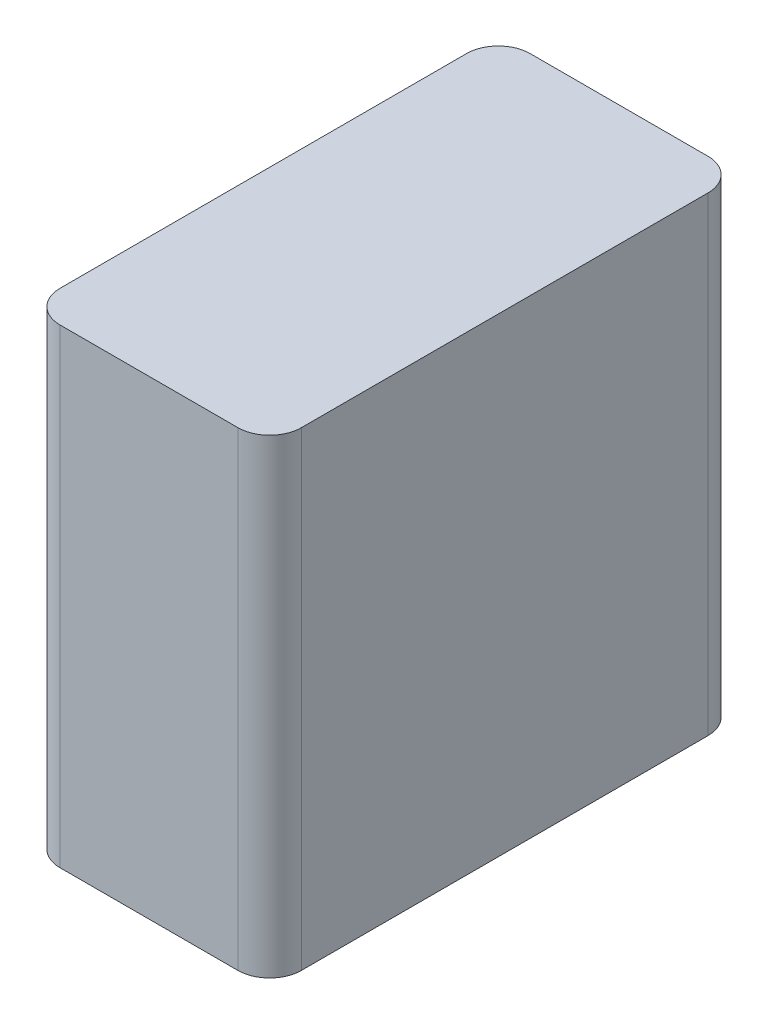
SolidWorks part; units mm, degrees
ref_plane "Front" through (0, 0, 0) normal (0, 0, 1) x (1, 0, 0)
ref_plane "Top" through (0, 0, 0) normal (0, 1, 0) x (1, 0, 0)
ref_plane "Right" through (0, 0, 0) normal (1, 0, 0) x (0, 0, -1)
sketch "Sketch1" plane through (0, 0, 0) normal (1, 0, 0) x (0, 0, -1)
  line L1 (0, 0) -> (74, 0)
  line L2 (0, 0) -> (0, 74)
  line L3 (0, 74) -> (74, 74)
  line L4 (74, 0) -> (74, 74)
  dimension "D1" = 74
  dimension "D2" = 74
extrude "Boss-Extrude1" add sketch "Sketch1" along normal blind 38
fillet "Fillet1" radius 5 4 edges at (0, 37, 0) (38, 37, 0) (38, 37, -74) (0, 37, -74)
